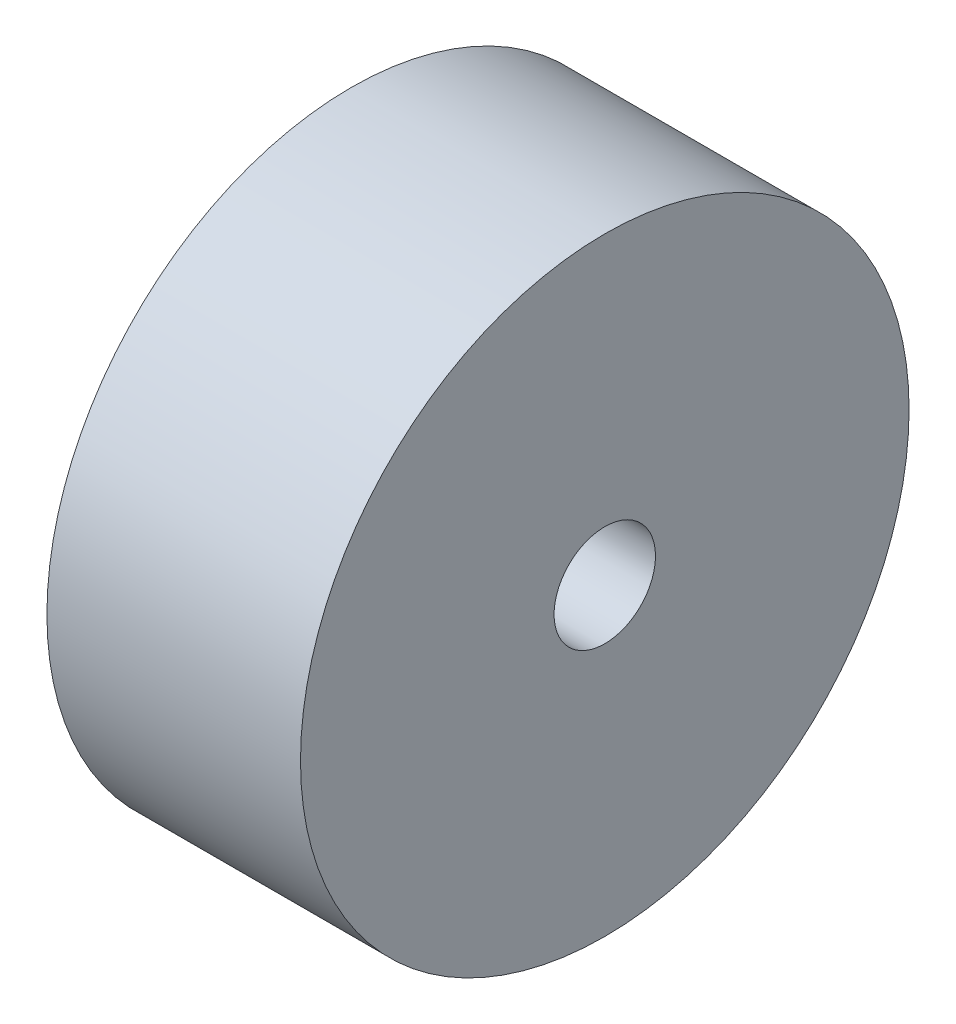
SolidWorks part; units mm, degrees
material "POLYURETHANE (11671)"
ref_plane "Front" through (0, 0, 0) normal (0, 0, 1) x (1, 0, 0)
ref_plane "Top" through (0, 0, 0) normal (0, 1, 0) x (1, 0, 0)
ref_plane "Right" through (0, 0, 0) normal (1, 0, 0) x (0, 0, -1)
sketch "Sketch1" plane through (0, 0, 0) normal (1, 0, 0) x (0, 0, -1)
  circle A0 centre (0, 0) radius 152.4
  circle A1 centre (0, 0) radius 25.4
  dimension "D1" = 50.8
  dimension "D2" = 304.8
extrude "Boss-Extrude1" add sketch "Sketch1" along normal blind 127
